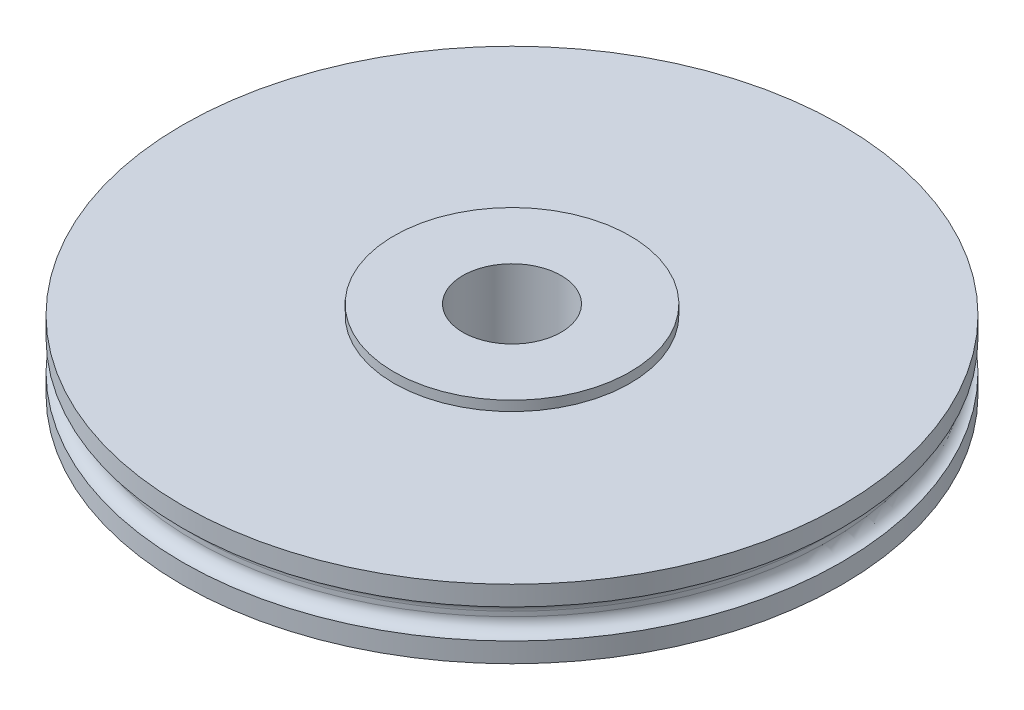
SolidWorks part; units mm, degrees
ref_plane "Front Plane" through (0, 0, 0) normal (0, 0, 1) x (1, 0, 0)
ref_plane "Top Plane" through (0, 0, 0) normal (0, 1, 0) x (1, 0, 0)
ref_plane "Right Plane" through (0, 0, 0) normal (1, 0, 0) x (0, 0, -1)
sketch "Sketch1" plane through (0, 0, 0) normal (0, 1, 0) x (1, 0, 0)
  circle A0 centre (0, 0) radius 26.5906
  dimension "D1" = 53.1812
extrude "Boss-Extrude1" add sketch "Sketch1" along normal blind 1.5875
sketch "Sketch2" plane through (0, 1.5875, 0) normal (0, 1, 0) x (1, 0, 0)
  circle A0 centre (0, 0) radius 25.5984
  dimension "D1" = 51.1969
extrude "Boss-Extrude2" add sketch "Sketch2" along normal blind 2.3813
sketch "Sketch3" plane through (0, 3.9688, 0) normal (0, 1, 0) x (1, 0, 0)
  circle A0 centre (0, 0) radius 26.5906
extrude "Boss-Extrude3" add sketch "Sketch3" along normal blind 1.5875
sketch "Sketch5" plane through (0, 5.5563, 0) normal (0, 1, 0) x (1, 0, 0)
  circle A0 centre (0, 0) radius 9.525
extrude "Boss-Extrude4" add sketch "Sketch5" along normal blind 0.7937
sketch "Sketch6" plane through (0, 6.35, 0) normal (0, 1, 0) x (1, 0, 0)
  circle A0 centre (0, 0) radius 3.9688
  dimension "D1" = 7.9375
extrude "Cut-Extrude1" cut sketch "Sketch6" against normal through all
fillet "Fillet1" radius 1 1 edges at (0, 1.5875, 25.5984)
fillet "Fillet2" radius 1 1 edges at (0, 3.9688, 25.5984)
